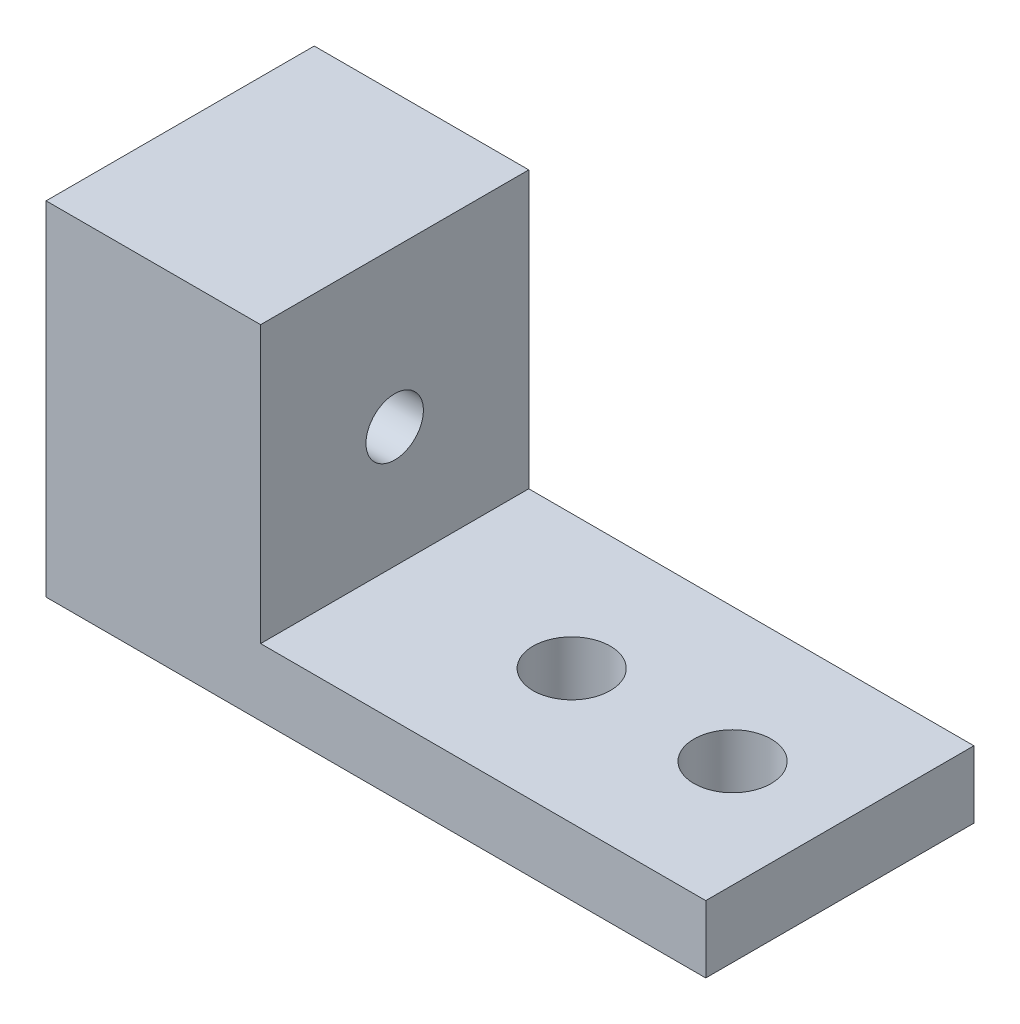
SolidWorks part; units mm, degrees
material "Plain Carbon Steel"
ref_plane "Front Plane" through (0, 0, 0) normal (0, 0, 1) x (1, 0, 0)
ref_plane "Top Plane" through (0, 0, 0) normal (0, 1, 0) x (1, 0, 0)
ref_plane "Right Plane" through (0, 0, 0) normal (1, 0, 0) x (0, 0, -1)
sketch "Sketch1" plane through (0, 0, 0) normal (0, 0, 1) x (1, 0, 0)
  line L0 (0, 0) -> (0, 16.256)
  line L1 (0, 16.256) -> (10.16, 16.256)
  line L2 (10.16, 16.256) -> (10.16, 3.175)
  line L3 (10.16, 3.175) -> (31.242, 3.175)
  line L4 (31.242, 3.175) -> (31.242, 0)
  line L5 (31.242, 0) -> (0, 0)
  dimension "D1" = 10.16
  dimension "D2" = 3.175
  dimension "D4" = 16.256
  dimension "D3" = 21.082
extrude "Boss-Extrude1" add sketch "Sketch1" against normal mid plane 12.7
sketch "Sketch2" plane through (0, 0, 0) normal (-1, 0, 0) x (0, 0, 1)
  circle A0 centre (0, 8.89) radius 1.3589
  dimension "D1" = 2.7178
  dimension "D2" = 8.89
extrude "Cut-Extrude1" cut sketch "Sketch2" against normal up to next
sketch "Sketch3" plane through (0, 0, 0) normal (0, -1, 0) x (1, 0, 0)
  circle A0 centre (18.542, 0) radius 1.8288
  dimension "D1" = 3.6576
  dimension "D2" = 8.382
extrude "Cut-Extrude2" cut sketch "Sketch3" against normal up to next
pattern_linear "LPattern1" count 2 spacing 7.62 along (1, 0, 0) of "Cut-Extrude2"
equation "\"D2@Sketch1\"=1/8"
equation "\"Middle Coupler Inner Daimeter\"= 3.875in"
equation "\"Middle Coupler  Wall Thickness\" = 0.25in"
equation "\"Middle Coupler Bottom Thickness\"= 0.2in"
equation "\"Bearing Rail Offset\"= 0.45in"
equation "\"3-56 UNF Tap\"= 0.089in"
equation "\"3-48 Tap\"= 0.079in"
equation "\"3-56 UNF Clearance\"= 0.104in"
equation "\"3-48 Clearance\" = 0.104in"
equation "\"Ball Bearing Distance\"= 0.03in"
equation "\"TCA Outer Diameter\" = 6in"
equation "\"Interstage Aeroframe Wall Thickness\" = 0.072in"
equation "\"Compression Spring OD\"= 0.42in"
equation "\"10-24 Tap\"= 0.1495in"
equation "\"10-24 Clearance\"= 0.196in"
equation "\"Lower Stage Fuselage Wall Thickness\" = 0.25in"
equation "\"6-32 Tap\" = 0.107in"
equation "\"6-32 Clearance\" = 0.144in"
equation "\"1/4-20 Tap\" = 0.201in"
equation "\"12-24 Tap\" = 0.177in"
equation "\"12-24 Major Diameter\"= 0.216in"
equation "\"D1@Sketch2\"=\"6-32 Tap\""
equation "\"D1@Sketch3\"=\"6-32 Clearance\""
